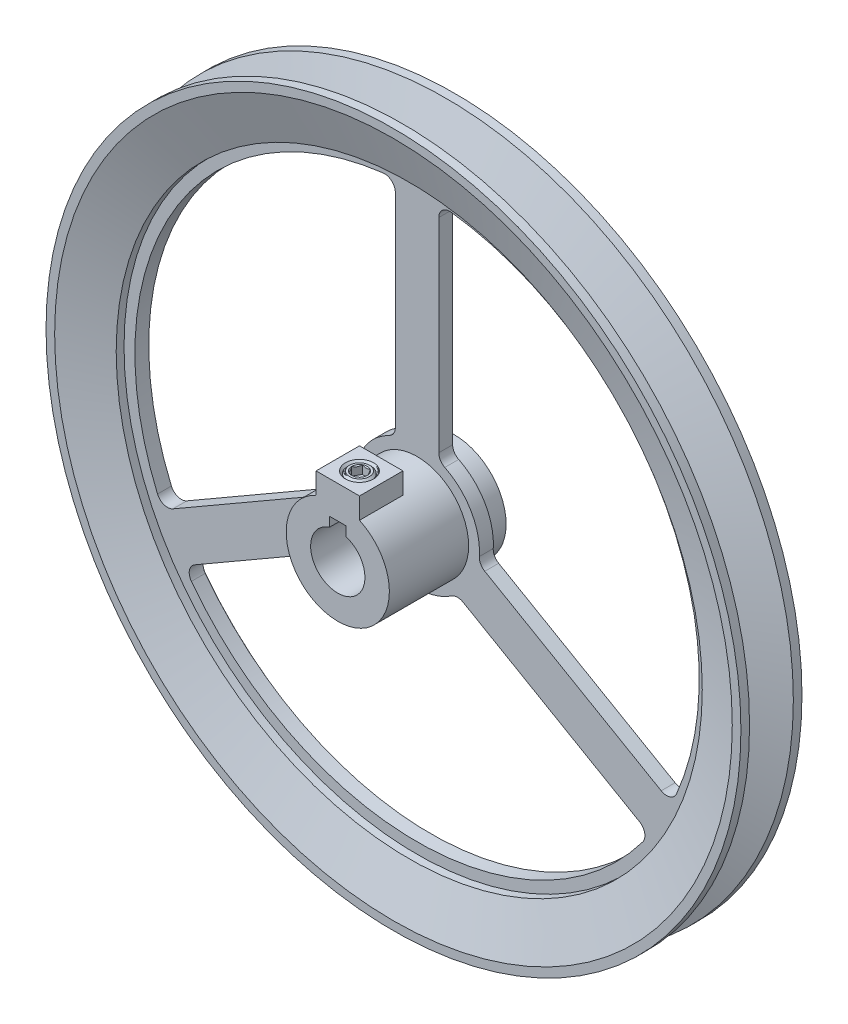
SolidWorks part; units mm, degrees
ref_plane "Front Plane" through (0, 0, 0) normal (0, 0, 1) x (1, 0, 0)
ref_plane "Top Plane" through (0, 0, 0) normal (0, 1, 0) x (1, 0, 0)
ref_plane "Right Plane" through (0, 0, 0) normal (1, 0, 0) x (0, 0, -1)
sketch "Sketch1" plane through (0, 0, 0) normal (1, 0, 0) x (0, 0, -1)
  line L0 (-25.2095, 0) -> (8.9281, 0) construction
  line L1 (-6.4018, 101.6) -> (6.4018, 101.6) construction
  line L2 (6.4018, 101.6) -> (8.9281, 101.6)
  line L5 (-8.9281, 101.6) -> (6.4018, 101.6) construction
  line L7 (-25.2095, 15.0812) -> (-25.2095, -15.0812) construction
  line L10 (-8.9281, 99.0737) -> (-4.3193, 85.6889)
  line L13 (-6.4018, 101.6) -> (-2.0289, 88.9)
  line L14 (-2.0289, 88.9) -> (2.0289, 88.9)
  line L15 (2.0289, 88.9) -> (6.4018, 101.6)
  line L16 (8.9281, 7.9375) -> (-25.2095, 7.9375) construction
  line L17 (0, 101.6) -> (0, 0) construction
  line L18 (-6.4018, 101.6) -> (-8.9281, 101.6)
  line L20 (-25.2095, 0) -> (-25.2095, 7.9375) construction
  line L22 (5.3086, 98.425) -> (-5.3086, 98.425) construction
  line L23 (8.9281, 101.6) -> (8.9281, 0) construction
  line L24 (8.9281, 99.0737) -> (4.3193, 85.6889)
  line L26 (-25.2095, 15.0812) -> (-8.5407, 15.0812)
  line L27 (-8.5407, 15.0812) -> (8.9281, 15.0813) construction
  line L28 (-4.3193, 85.6889) -> (4.3193, 85.6889) construction
  line L29 (-2.0289, 85.6889) -> (-2.0289, 15.0813)
  line L31 (-25.2095, 15.0812) -> (-25.2095, 0)
  line L32 (-8.9281, 99.0737) -> (-8.9281, 101.6)
  line L33 (8.9281, 101.6) -> (8.9281, 99.0737)
  line L34 (-25.2095, 0) -> (8.9281, 0)
  line L35 (8.9281, 0) -> (8.9281, 15.0813)
  line L36 (2.0289, 15.0813) -> (2.0289, 85.6889)
  line L37 (-2.0289, 15.0813) -> (2.0289, 15.0813) construction
  line L38 (-2.0289, 88.9) -> (-5.065, 87.8546) construction
  line L39 (-8.5407, 15.0812) -> (-2.0289, 15.0813)
  line L40 (8.9281, 15.0813) -> (2.0289, 15.0813)
  line L41 (-2.0289, 88.9) -> (-2.0289, 85.6889) construction
  line L42 (-8.5407, 15.0812) -> (-8.5407, 0) construction
  line L43 (-4.3193, 85.6889) -> (-2.0289, 85.6889)
  line L44 (4.3193, 85.6889) -> (2.0289, 85.6889)
  point P6 (0, 15.0813)
  point P16 (0, 88.9)
  point P25 (-8.5407, 0)
  point P38 (0, 85.6889)
revolve "Revolve1" add sketch "Sketch1" angle 360 about L0
sketch "Sketch2" plane through (0, -7.9375, -8.9281) normal (0, 0, 1) x (0, 1, 0)
  line L2 (109.5375, 0) -> (7.9375, 0) construction
  line L3 (7.9375, 0) -> (-42.8625, -87.9882) construction
  line L6 (-25.9458, -71.3876) -> (3.8376, -19.8012)
  line L9 (27.1358, -6.35) -> (86.7026, -6.35)
  arc A0 (6.7873, -18.22) -> (24.2916, -8.1139) centre (7.9375, 0) ccw
  arc A1 (-24.4421, -75.8954) -> (89.8546, -9.9062) centre (7.9375, 0) ccw
  circle A2 centre (7.9375, 0) radius 101.6 construction
  arc A3 (-24.4421, -75.8954) -> (-25.9458, -71.3876) centre (-23.1961, -72.9751) cw
  arc A4 (89.8546, -9.9062) -> (86.7026, -6.35) centre (86.7026, -9.525) ccw
  arc A5 (27.1358, -6.35) -> (24.2916, -8.1139) centre (27.1358, -9.525) ccw
  arc A6 (3.8376, -19.8012) -> (6.7873, -18.22) centre (6.5873, -21.3887) cw
  circle A7 centre (7.9375, 0) radius 85.6889 construction
  circle A8 centre (7.9375, 0) radius 15.0813 construction
  dimension "D1" = 3.175
  dimension "D2" = 12.7
  dimension "D3" = 12.7
  dimension "D4" = 120
  dimension "D5" = 3.175
  dimension "D6" = 3.175
extrude "Cut-Extrude1" cut sketch "Sketch2" along normal up to surface (17.8562 mm away) up to face at (99.0737, 0, 8.9281)
pattern_circular "CirPattern1" count 3 over 360 about axis through (0, 0, 0) along (0, 0, 1) of "Cut-Extrude1"
sketch "Sketch3" plane through (0, 0, -8.9281) normal (0, 0, -1) x (-1, 0, 0)
  circle A0 centre (0, 0) radius 7.9375
  circle A1 centre (0, 0) radius 98.425 construction
  point P4 (0, 7.9375)
extrude "Cut-Extrude2" cut sketch "Sketch3" against normal up to vertex (34.1376 mm away) up to point (0, 0, 25.2095)
sketch "Sketch4" plane through (0, 0, -8.9281) normal (0, 0, -1) x (-1, 0, 0)
  line L0 (2.3812, 7.9375) -> (-2.3812, 7.9375) construction
  line L1 (2.3813, 10.3187) -> (-2.3813, 10.3187)
  line L2 (2.3813, 10.3187) -> (2.3812, 5.5562)
  line L3 (2.3812, 5.5562) -> (-2.3812, 5.5562)
  line L4 (-2.3813, 10.3187) -> (-2.3812, 5.5562)
  dimension "Keyway Wd." = 4.7625
  dimension "Keyway Dp." = 2.3813
extrude "Cut-Extrude3" cut sketch "Sketch4" against normal up to vertex (34.1376 mm away) up to point (0, 0, 25.2095)
ref_plane "Plane1" through (0, 15.0812, 0) normal (0, 1, 0) x (-1, 0, 0)
sketch "Sketch5" plane through (0, 15.0812, 0) normal (0, 1, 0) x (-1, 0, 0)
  line L0 (0, 25.2095) -> (0, 0) construction
  line L1 (6.35, 12.5095) -> (-6.35, 12.5095)
  line L2 (6.35, 12.5095) -> (6.35, 25.2095)
  line L3 (6.35, 25.2095) -> (-6.35, 25.2095)
  line L4 (-6.35, 12.5095) -> (-6.35, 25.2095)
  line L5 (15.0812, 25.2095) -> (-15.0812, 25.2095) construction
  dimension "D1" = 12.7
extrude "Boss-Extrude1" add sketch "Sketch5" against normal up to surface (6.1645 mm away) from offset 4.7625 up to face at (15.0812, 0, 25.2095)
sketch "Sketch6" plane through (0, 19.8438, 0) normal (0, 1, 0) x (-1, 0, 0)
  line L0 (0, 12.5095) -> (0, 25.2095) construction
  line L1 (6.35, 25.2095) -> (-6.35, 25.2095) construction
  line L2 (-6.35, 12.5095) -> (6.35, 12.5095) construction
  line L7 (0, 22.8283) -> (0, 21.4171) construction
  circle A0 centre (0, 18.8595) radius 3.9688 construction
  circle A1 centre (0, 18.8595) radius 3.0868
  dimension "D3" = 0.8819
extrude "Cut-Extrude4" cut sketch "Sketch6" against normal up to vertex (19.8438 mm away) up to point (0, 0, 25.2095)
sketch "Sketch7" plane through (0, 19.8438, 0) normal (0, 1, 0) x (-1, 0, 0)
  circle A0 centre (0, 18.8595) radius 3.9688 construction
  circle A1 centre (0, 18.8595) radius 3.9688
  point P3 (0, 22.8283)
curve "Helix/Spiral1" pitch 1.4111 height 16.4924 turns 11.6875
sketch "Sketch8" plane through (0, 0, 0) normal (1, 0, 0) x (0, 0, -1)
  line L0 (-21.7589, 21.2549) -> (-21.7589, 19.8438) construction
  line L1 (-21.7589, 19.8438) -> (-22.981, 20.5493) construction
  line L2 (-22.981, 20.5493) -> (-21.7589, 21.2549) construction
  line L3 (-21.7589, 19.8438) -> (-22.8283, 19.8438) construction
  line L4 (-22.8283, 19.8438) -> (-22.8283, 20.4611) construction
  line L5 (-22.8283, 20.4611) -> (-22.8283, 20.6375) construction
  line L6 (-21.9117, 19.9319) -> (-21.9117, 21.1667) construction
  line L7 (-22.981, 20.5493) -> (-22.8283, 20.5493) construction
  line L8 (-21.9117, 20.5493) -> (-21.7589, 20.5493) construction
  line L9 (-21.8353, 21.2108) -> (-21.8353, 19.8878)
  line L10 (-21.8353, 19.8878) -> (-22.8283, 20.4611)
  line L11 (-22.8283, 20.4611) -> (-22.8283, 20.6375)
  line L12 (-22.8283, 20.6375) -> (-21.8353, 21.2108)
  point P16 (-21.8353, 20.5493)
  dimension "D1" = 1.4111
  dimension "D2" = 0.1764
sweep "Cut-Sweep1" cut profiles "Sketch8" path "Helix/Spiral1" align with end faces yes
sketch "Sketch9" plane through (0, 19.8438, 0) normal (0, 1, 0) x (-1, 0, 0)
  circle A0 centre (0, 18.8595) radius 4.1215
extrude "Cut-Extrude5" cut sketch "Sketch9" against normal through all draft 45
sketch "Sketch10" plane through (0, 0, 0) normal (1, 0, 0) x (0, 0, -1)
  line L0 (-18.8595, 19.8438) -> (-18.8595, 10.3187) construction
  line L1 (-22.8283, 11.3881) -> (-22.8283, 18.7744)
  line L2 (-18.8595, 19.8438) -> (-22.8283, 19.8438) construction
  line L3 (-18.8595, 19.8438) -> (-18.8595, 10.3187)
  line L4 (-18.8595, 10.3187) -> (-22.8283, 10.3187) construction
  line L5 (-22.8283, 19.8438) -> (-22.8283, 10.3187) construction
  line L6 (-21.7589, 19.8438) -> (-22.8283, 18.7744)
  line L7 (-22.8283, 11.3881) -> (-21.7589, 10.3187)
  line L8 (-21.7589, 19.8438) -> (-18.8595, 19.8438)
  line L9 (-21.7589, 10.3187) -> (-18.8595, 10.3187)
  line L10 (-12.5095, 19.8438) -> (-25.2095, 19.8438) construction
  line L11 (-21.7589, 19.8438) -> (-22.8283, 19.8438) construction
  line L12 (-22.8283, 19.8438) -> (-22.8283, 18.7744) construction
revolve "Revolve3" add sketch "Sketch10" angle 360 about L0
sketch "Sketch11" plane through (0, 19.8438, 0) normal (0, 1, 0) x (-1, 0, 0)
  circle A1 centre (0, 18.8595) radius 3.9688
  circle A2 centre (0, 18.8595) radius 3.9688
  dimension "D1" = 0
curve "Helix/Spiral2" pitch 1.4111 height 10.9361 turns 7.75
sketch "Sketch12" plane through (0, 0, 0) normal (1, 0, 0) x (0, 0, -1)
  line L0 (-22.9046, 20.5052) -> (-22.9046, 19.1823)
  line L1 (-22.9046, 20.5493) -> (-22.9046, 20.5052) construction
  line L2 (-22.981, 20.5493) -> (-22.8283, 20.5493) construction
  line L3 (-21.7589, 19.8438) -> (-22.981, 20.5493) construction
  line L4 (-22.9046, 20.5052) -> (-21.9117, 19.9319)
  line L5 (-21.9117, 19.9319) -> (-21.9117, 19.7556)
  line L6 (-21.9117, 19.7556) -> (-22.9046, 19.1823)
  line L7 (-22.981, 20.5493) -> (-21.7589, 19.8438) construction
  line L8 (-21.7589, 19.8438) -> (-22.981, 19.1382) construction
  line L9 (-22.981, 19.1382) -> (-22.981, 20.5493) construction
sweep "Cut-Sweep2" cut profiles "Sketch12" path "Helix/Spiral2" align with end faces yes
sketch "Sketch13" plane through (0, 19.8438, 0) normal (0, 1, 0) x (1, 0, 0)
  line L1 (2.2914, -18.8595) -> (1.1457, -16.8751)
  line L2 (1.1457, -16.8751) -> (-1.1457, -16.8751)
  line L3 (-1.1457, -16.8751) -> (-2.2914, -18.8595)
  line L4 (-2.2914, -18.8595) -> (-1.1457, -20.8439)
  line L5 (-1.1457, -20.8439) -> (1.1457, -20.8439)
  line L6 (1.1457, -20.8439) -> (2.2914, -18.8595)
  circle A0 centre (0, -18.8595) radius 1.9844 construction
  dimension "D1" = 3.9688
extrude "Cut-Extrude6" cut sketch "Sketch13" against normal blind 2.4805
sketch "Sketch14" plane through (0, 19.8438, 0) normal (0, 1, 0) x (1, 0, 0)
  circle A0 centre (0, -18.8595) radius 2.2914
extrude "Cut-Extrude7" cut sketch "Sketch14" against normal through all draft 45
equation "\"D3@Sketch6\" = \"Screw Pitch@Sketch6\" * 5 / 8"
equation "\"D4@Helix/Spiral1\" = \"Screw Pitch@Sketch6\""
equation "\"D3@Helix/Spiral1\" = \"D4@Helix/Spiral1\" + ( \"Hub Dia.@Sketch1\" / 2 ) "
equation "\"D1@Sketch8\" = \"D4@Helix/Spiral1\""
equation "\"D2@Sketch8\" = \"D1@Sketch8\" / 8"
equation "\"D4@Helix/Spiral2\" = \"D4@Helix/Spiral1\""
equation "\"D3@Helix/Spiral2\" = \"D4@Helix/Spiral2\" + \"Screw Length@Sketch10\""
equation "\"D1@Sketch13\" = \"Screw OD@Sketch6\" / 2"
equation "\"D1@Cut-Extrude6\" = \"D1@Sketch13\" * 5 / 8"
equation "\"D4@Sketch2\" = \"D3@CirPattern1\" / \"Spokes@CirPattern1\""
